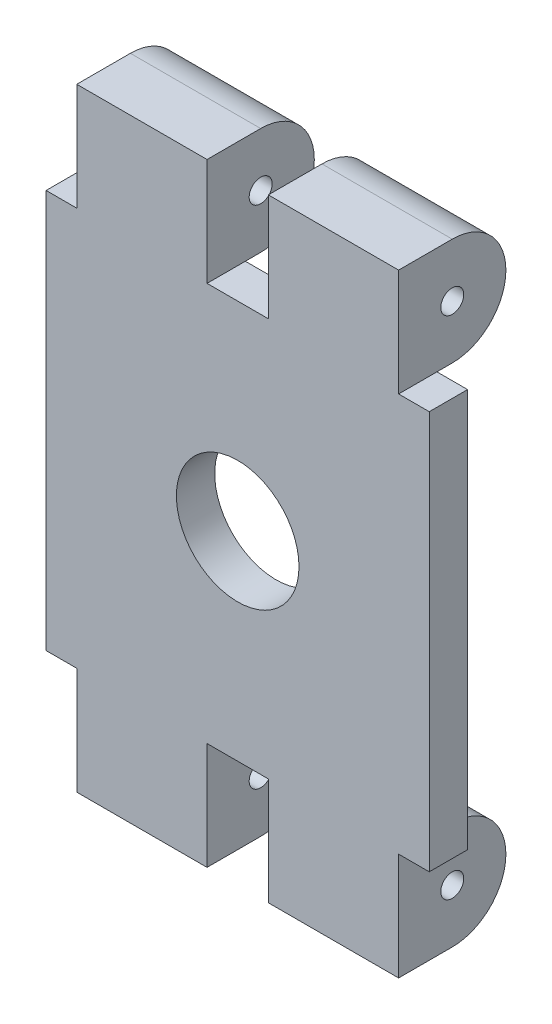
SolidWorks part; units mm, degrees
ref_plane "前视基准面" through (0, 0, 0) normal (0, 0, 1) x (1, 0, 0)
ref_plane "上视基准面" through (0, 0, 0) normal (0, 1, 0) x (1, 0, 0)
ref_plane "右视基准面" through (0, 0, 0) normal (1, 0, 0) x (0, 0, -1)
sketch "草图1" plane through (0, 0, 0) normal (0, 0, 1) x (1, 0, 0)
  line L1 (-25, 40) -> (25, 40)
  line L2 (-25, 40) -> (-25, -40)
  line L3 (-25, -40) -> (25, -40)
  line L4 (25, 40) -> (25, -40)
  line L5 (-25, 40) -> (25, -40) construction
  line L6 (-25, -40) -> (25, 40) construction
  point P0 (0, 0)
  dimension "D1" = 50
  dimension "D2" = 80
extrude "凸台-拉伸1" add sketch "草图1" along normal blind 5
sketch "草图3" plane through (-25, 0, 0) normal (-1, 0, 0) x (0, 0, 1)
  line L0 (5, 40) -> (5, -40) construction
  line L1 (5, 40) -> (0, 40) construction
  line L2 (5, 40) -> (-2, 40)
  line L3 (-2, 26) -> (5, 26)
  line L4 (5, 26) -> (5, 40)
  line L5 (0, 0) -> (5, 0) construction
  line L6 (5, -26) -> (5, -40)
  line L7 (-2, -26) -> (5, -26)
  line L8 (5, -40) -> (-2, -40)
  arc A0 (-2, 40) -> (-2, 26) centre (-2, 33) ccw
  arc A1 (-2, -40) -> (-2, -26) centre (-2, -33) cw
  dimension "D1" = 14
extrude "凸台-拉伸2" add sketch "草图3" against normal blind 50
sketch "草图4" plane through (0, 0, 5) normal (0, 0, 1) x (1, 0, 0)
  line L0 (25, 40) -> (-25, 40) construction
  line L1 (-25, 40) -> (-21, 40)
  line L2 (-25, 40) -> (-25, 26)
  line L3 (-25, 26) -> (-21, 26)
  line L4 (-21, 40) -> (-21, 26)
  line L5 (-4, 40) -> (4, 40)
  line L6 (-4, 40) -> (-4, 26)
  line L7 (-4, 26) -> (4, 26)
  line L8 (4, 40) -> (4, 26)
  line L9 (-25, 0) -> (25, 0) construction
  line L10 (25, 40) -> (21, 40)
  line L11 (25, 40) -> (25, 26)
  line L12 (25, 26) -> (21, 26)
  line L13 (21, 40) -> (21, 26)
  line L14 (-25, 40) -> (-25, -40) construction
  line L15 (25, -40) -> (25, 40) construction
  line L16 (21, -40) -> (21, -26)
  line L17 (25, -26) -> (21, -26)
  line L18 (25, -40) -> (25, -26)
  line L19 (25, -40) -> (21, -40)
  line L20 (4, -40) -> (4, -26)
  line L21 (-4, -26) -> (4, -26)
  line L22 (-4, -40) -> (-4, -26)
  line L23 (-4, -40) -> (4, -40)
  line L24 (-21, -40) -> (-21, -26)
  line L25 (-25, -26) -> (-21, -26)
  line L26 (-25, -40) -> (-25, -26)
  line L27 (-25, -40) -> (-21, -40)
  dimension "D1" = 4
  dimension "D2" = 4
  dimension "D3" = 8
  dimension "D4" = 17
  dimension "D5" = 14
extrude "切除-拉伸1" cut sketch "草图4" against normal blind 50
sketch "草图5" plane through (-25, 0, 0) normal (-1, 0, 0) x (0, 0, 1)
  circle A0 centre (-2, 33) radius 1.5
  circle A1 centre (-2, -33) radius 1.5
  dimension "D1" = 3
  dimension "D2" = 3
extrude "切除-拉伸2" cut sketch "草图5" against normal blind 50
sketch "草图6" plane through (0, 0, 5) normal (0, 0, 1) x (1, 0, 0)
  circle A0 centre (0, 0) radius 8
  dimension "D1" = 16
extrude "切除-拉伸3" cut sketch "草图6" against normal blind 50
